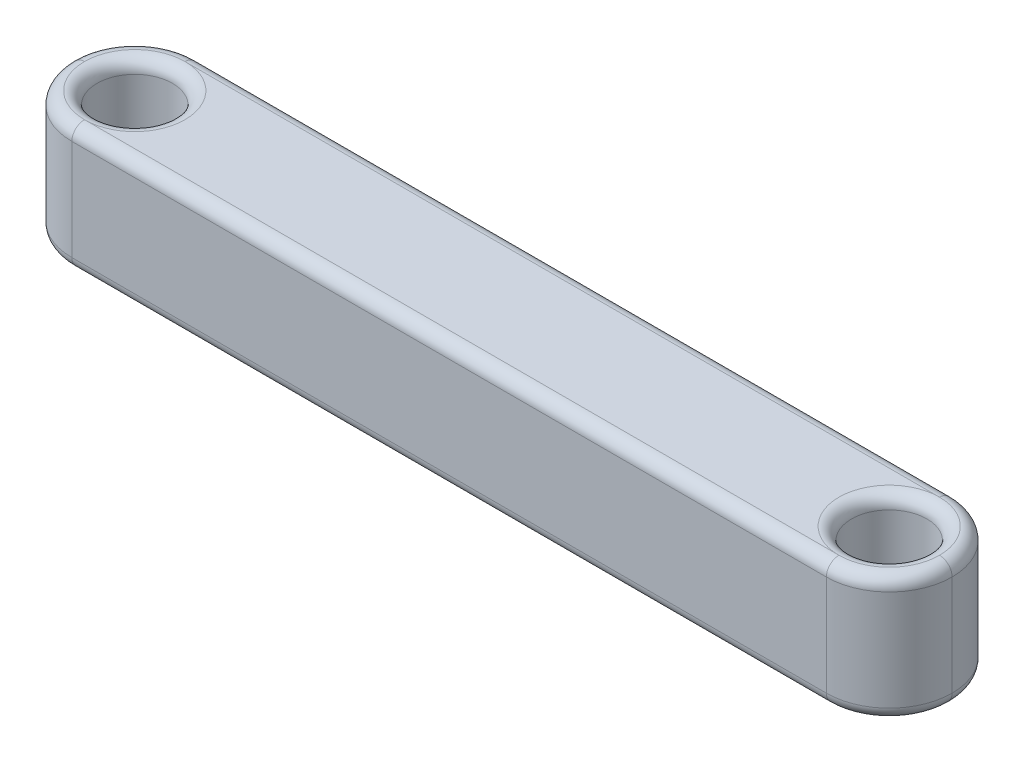
SolidWorks part; units mm, degrees
ref_plane "Front Plane" through (0, 0, 0) normal (0, 0, 1) x (1, 0, 0)
ref_plane "Top Plane" through (0, 0, 0) normal (0, 1, 0) x (1, 0, 0)
ref_plane "Right Plane" through (0, 0, 0) normal (1, 0, 0) x (0, 0, -1)
sketch "Sketch1" plane through (0, 0, 0) normal (0, 1, 0) x (1, 0, 0)
  line L1 (-17.5, -2.5) -> (17.5, -2.5)
  line L2 (-17.5, -2.5) -> (-17.5, 2.5)
  line L3 (-17.5, 2.5) -> (17.5, 2.5)
  line L4 (17.5, -2.5) -> (17.5, 2.5)
  line L5 (-17.5, -2.5) -> (17.5, 2.5) construction
  line L6 (-17.5, 2.5) -> (17.5, -2.5) construction
  point P0 (0, 0)
  dimension "D1" = 35
  dimension "D2" = 5
extrude "Boss-Extrude1" add sketch "Sketch1" along normal blind 5
sketch "Sketch2" plane through (0, 5, 0) normal (0, 1, 0) x (1, 0, 0)
  line L0 (-17.5, 2.5) -> (-17.5, -2.5) construction
  line L1 (17.5, -2.5) -> (17.5, 2.5) construction
  circle A0 centre (-15, 0) radius 1.5
  circle A1 centre (15, 0) radius 1.5
  point P7 (-17.5, 0)
  point P11 (17.5, 0)
  dimension "D1" = 2.5
  dimension "D3" = 3
  dimension "D2" = 2.5
extrude "Cut-Extrude1" cut sketch "Sketch2" against normal through all
fillet "Fillet1" radius 2.5 4 edges at (17.5, 2.5, -2.5) (17.5, 2.5, 2.5) (-17.5, 2.5, -2.5) (-17.5, 2.5, 2.5)
fillet "Fillet2" radius 0.5 16 edges at (-16.7678, 0, -1.7678) (-16.7678, 0, 1.7678) (0, 0, 2.5) (16.7678, 0, 1.7678) (16.7678, 0, -1.7678) (0, 0, -2.5) (15, 0, 1.5) (-15, 0, 1.5) (0, 5, 2.5) (-16.7678, 5, 1.7678) (-16.7678, 5, -1.7678) (0, 5, -2.5) (16.7678, 5, -1.7678) (16.7678, 5, 1.7678) (15, 5, 1.5) (-15, 5, 1.5)
